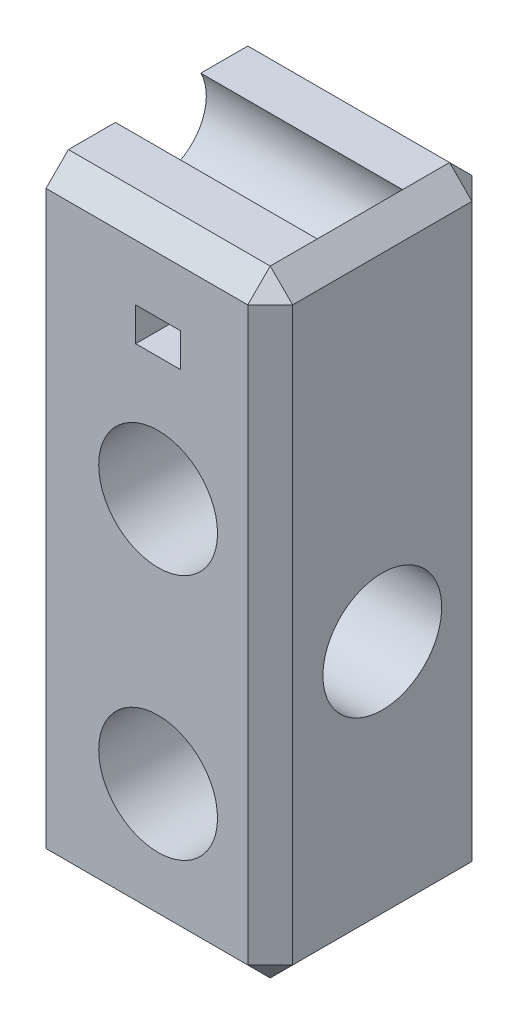
SolidWorks part; units mm, degrees
ref_plane "Front Plane" through (0, 0, 0) normal (0, 0, 1) x (1, 0, 0)
ref_plane "Top Plane" through (0, 0, 0) normal (0, 1, 0) x (1, 0, 0)
ref_plane "Right Plane" through (0, 0, 0) normal (1, 0, 0) x (0, 0, -1)
sketch "Sketch1" plane through (0, 0, 0) normal (0, 1, 0) x (1, 0, 0)
  line L0 (-10, -10) -> (10, 10) construction
  line L1 (-10, 10) -> (10, 10)
  line L2 (-10, 10) -> (-10, -10)
  line L3 (-10, -10) -> (10, -10)
  line L4 (10, 10) -> (10, -10)
  dimension "D1" = 20
extrude "Boss-Extrude1" add sketch "Sketch1" along normal blind 55
sketch "Sketch2" plane through (0, 0, 10) normal (0, 0, 1) x (1, 0, 0)
  line L0 (0, 0) -> (0, 12) construction
  line L1 (0, 12) -> (0, 34) construction
  line L2 (0, 55) -> (0, 45) construction
  line L3 (-10, 55) -> (10, 55) construction
  line L5 (-2, 48) -> (2, 48)
  line L6 (-2, 48) -> (-2, 45)
  line L7 (-2, 45) -> (2, 45)
  line L8 (2, 48) -> (2, 45)
  circle A0 centre (0, 12) radius 5.3
  circle A1 centre (0, 34) radius 5.3
  dimension "D1" = 12
  dimension "D3" = 10.6
  dimension "D2" = 22
  dimension "D4" = 4
  dimension "D5" = 3
  dimension "D6" = 10
extrude "Cut-Extrude1" cut sketch "Sketch2" against normal through all and the other way through all
sketch "Sketch3" plane through (-10, 0, 0) normal (-1, 0, 0) x (0, 0, 1)
  line L0 (0, 0) -> (0, 23) construction
  circle A0 centre (0, 23) radius 5.3
  dimension "D2" = 10.6
  dimension "D3" = 23
extrude "Cut-Extrude2" cut sketch "Sketch3" against normal through all contours A0
sketch "Sketch4" plane through (-10, 0, 0) normal (-1, 0, 0) x (0, 0, 1)
  line L0 (0, 53) -> (0, 55) construction
  line L1 (-10, 55) -> (10, 55) construction
  circle A0 centre (0, 53) radius 4.3
  dimension "D1" = 8.6
  dimension "D2" = 2
extrude "Cut-Extrude3" cut sketch "Sketch4" against normal blind 18
chamfer "Chamfer1" distance 2 angle 45 8 edges at (0, 0, -10) (10, 0, 0) (0, 0, 10) (10, 27.5, -10) (0, 55, -10) (10, 55, 0) (0, 55, 10) (10, 27.5, 10)
